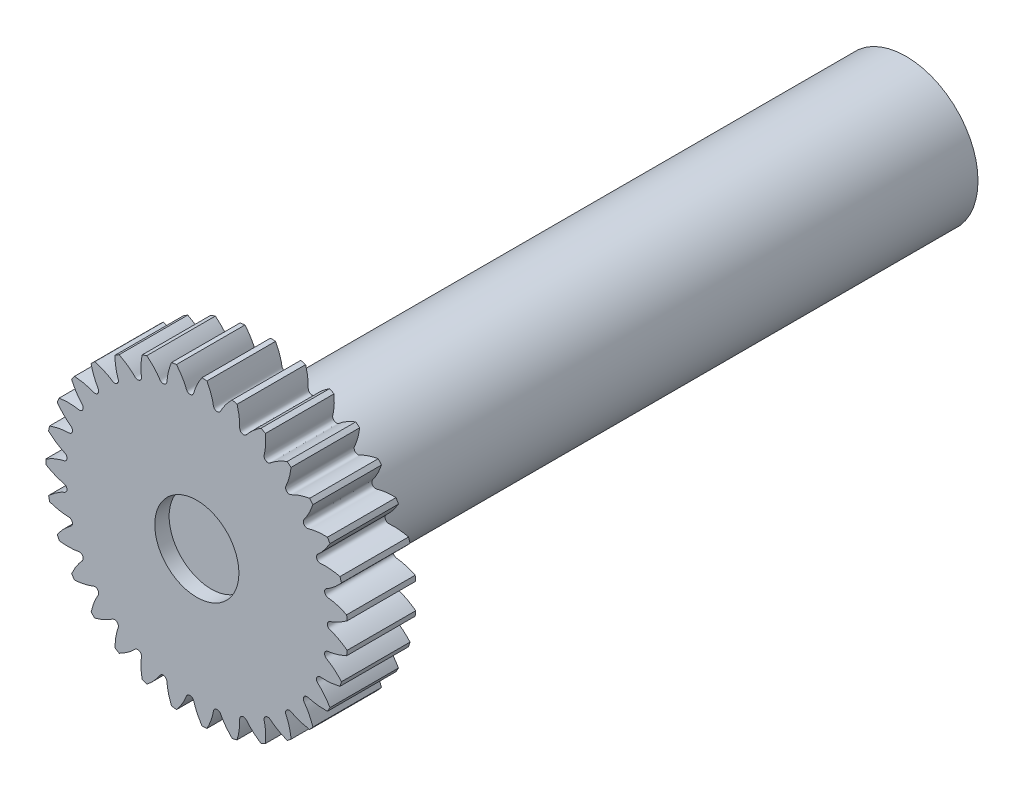
SolidWorks part; units mm, degrees
ref_plane "Front Plane" through (0, 0, 0) normal (0, 0, 1) x (1, 0, 0)
ref_plane "Top Plane" through (0, 0, 0) normal (0, 1, 0) x (1, 0, 0)
ref_plane "Right Plane" through (0, 0, 0) normal (1, 0, 0) x (0, 0, -1)
ref_axis "Axis1" through (0, 0, 10.4775) along (0, 0, -1)
sketch "SketchRevolveSpurGear" plane through (0, 0, 0) normal (1, 0, 0) x (0, 0, -1)
  line L0 (0, 0) -> (1, 0) construction
  line L1 (-9.525, 0) -> (-9.525, 41.91)
  line L2 (-9.525, 41.91) -> (9.525, 41.91)
  line L3 (9.525, 41.91) -> (9.525, 0)
  line L4 (9.525, 0) -> (-9.525, 0)
  dimension "Side1" = 9.525
  dimension "OutsideRadius" = 41.91
  dimension "Side2" = 9.525
revolve "SpurGear" add sketch "SketchRevolveSpurGear" angle 360 about L0
sketch "SketchToothSpurGear" plane through (0, 0, 0) normal (0, 0, 1) x (1, 0, 0)
  arc A0 (41.8798, 3.6317) -> (41.8798, -3.6317) centre (0, 0) cw
  spline S0 degree 3 poles (41.8798, -3.6317) (41.6691, -3.4736) (41.3536, -3.2456) (40.9313, -2.958) (40.6258, -2.758) (40.3267, -2.57) (40.0345, -2.3936) (39.7495, -2.2287) (39.472, -2.0747) (39.2023, -1.9316) (38.9406, -1.7988) (38.6874, -1.676) (38.4429, -1.5629) (38.2072, -1.4591) (37.9808, -1.3644) (37.7638, -1.278) (37.5563, -1.2003) (37.2984, -1.1071) (37.0822, -1.0439) (36.9181, -0.9716) (36.8523, -0.9389) (36.7866, -0.9022) (36.721, -0.8604) (36.6553, -0.8126) (36.5895, -0.7571) (36.524, -0.6924) (36.46, -0.6162) (36.3996, -0.5269) (36.3459, -0.4231) (36.3031, -0.3051) (36.2781, -0.1818) (36.2702, -0.0787) (36.2715, 0) (36.2702, 0.0787) (36.2781, 0.1818) (36.3031, 0.3051) (36.3459, 0.4231) (36.3996, 0.5269) (36.46, 0.6162) (36.524, 0.6924) (36.5895, 0.7571) (36.6553, 0.8126) (36.721, 0.8604) (36.7866, 0.9022) (36.8523, 0.9389) (36.9181, 0.9716) (37.0822, 1.0439) (37.2984, 1.1071) (37.5563, 1.2003) (37.7638, 1.278) (37.9808, 1.3644) (38.2072, 1.4591) (38.4429, 1.5629) (38.6874, 1.676) (38.9406, 1.7988) (39.2023, 1.9316) (39.472, 2.0747) (39.7495, 2.2287) (40.0345, 2.3936) (40.3267, 2.57) (40.6258, 2.758) (40.9313, 2.958) (41.3536, 3.2456) (41.6691, 3.4736) (41.8798, 3.6317) knots 0 0 0 0 0.057293 0.084638 0.111115 0.136724 0.161464 0.185337 0.208342 0.230478 0.251747 0.272148 0.291681 0.310345 0.328142 0.345071 0.361131 0.376324 0.404732 0.409978 0.41529 0.420719 0.426328 0.43219 0.438391 0.445027 0.452196 0.459984 0.468442 0.477551 0.487197 0.495694 0.5 0.504306 0.512803 0.522449 0.531558 0.540016 0.547804 0.554973 0.561609 0.56781 0.573672 0.579281 0.58471 0.590022 0.595268 0.623676 0.638869 0.654929 0.671858 0.689655 0.708319 0.727852 0.748253 0.769522 0.791658 0.814663 0.838536 0.863276 0.888885 0.915362 0.942707 1 1 1 1
extrude "ToothExtrudeCutSpurGear" cut sketch "SketchToothSpurGear" against normal blind 9.525 and the other way blind 9.525
pattern_circular "PatternSpurGear" count 31 every 11.613 about axis through (0, 0, 10.4775) along (0, 0, -1) of "ToothExtrudeCutSpurGear"
sketch "AuxiliarySketchSpurGear" plane through (0, 0, 0) normal (0, 0, 1) x (1, 0, 0)
  circle A0 centre (0, 0) radius 39.37 construction
  circle A1 centre (0, 0) radius 35.6813 construction
  circle A2 centre (0, 0) radius 37.1513 construction
  circle A3 centre (0, 0) radius 41.91 construction
  circle A4 centre (0, 0) radius 36.2712 construction
  dimension "PitchDiameter" = 78.74
  dimension "BaseDiameter" = 71.3627
  dimension "FormDiameter" = 74.3027
  dimension "MajorDiameter" = 83.82
  dimension "MinorDiameter" = 72.5424
scale "Scale1" bodies to scale 103 scale about centroid uniform scaling yes scale factor 0.5
sketch "Sketch1" plane through (0, 0, 4.7625) normal (0, 0, 1) x (1, 0, 0)
  circle A0 centre (0, 0) radius 5.845
extrude "Cut-Extrude1" cut sketch "Sketch1" against normal blind 2
sketch "Sketch3" plane through (0, 0, -4.7625) normal (0, 0, -1) x (-1, 0, 0)
  circle A0 centre (0, 0) radius 10
  dimension "D1" = 20
extrude "Boss-Extrude1" add sketch "Sketch3" along normal blind 89
